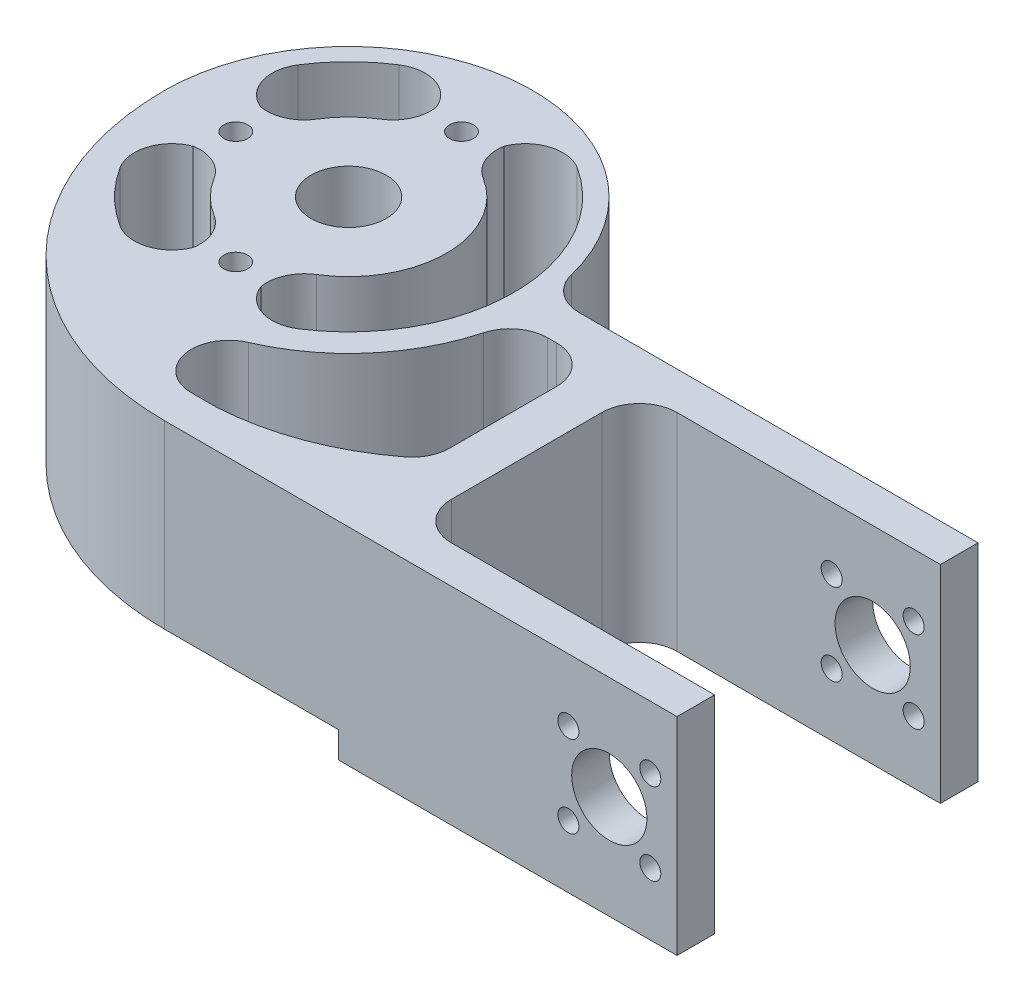
SolidWorks part; units mm, degrees
material "6061-T6 (SS)"
ref_plane "Front Plane" through (0, 0, 0) normal (0, 0, 1) x (1, 0, 0)
ref_plane "Top Plane" through (0, 0, 0) normal (0, 1, 0) x (1, 0, 0)
ref_plane "Right Plane" through (0, 0, 0) normal (1, 0, 0) x (0, 0, -1)
sketch "Sketch1" plane through (0, 0, 0) normal (0, 1, 0) x (1, 0, 0)
  circle A0 centre (0, 0) radius 31.0896
  dimension "D1" = 62.1792
extrude "Boss-Extrude1" add sketch "Sketch1" along normal blind 34.925
sketch "Sketch2" plane through (0, 34.925, 0) normal (0, 1, 0) x (1, 0, 0)
  line L0 (0, 0) -> (-31.0896, 0) construction
  line L1 (0, 0) -> (30.9857, 2.54) construction
  line L2 (46.5427, -48.26) -> (17.1704, -48.26)
  line L4 (46.5427, -48.26) -> (46.5427, 2.54)
  line L7 (30.9857, 2.54) -> (46.5427, 2.54)
  circle A0 centre (0, 0) radius 31.0896 construction
  arc A1 (17.1704, -48.26) -> (-31.0896, 0) centre (17.1704, 0) cw
  circle A2 centre (0, 0) radius 31.0896
  arc A3 (-31.0896, 0) -> (30.9857, 2.54) centre (0, 0) ccw
  dimension "D3" = 2.54
  dimension "D1" = 50.8
  dimension "D2" = 15.557
  dimension "D4" = 0
extrude "Boss-Extrude2" add sketch "Sketch2" against normal blind 30.48
sketch "Sketch3" plane through (0, 34.925, 0) normal (0, 1, 0) x (1, 0, 0)
  line L0 (46.5427, -0.3336) -> (46.5427, -48.26)
  line L1 (17.1704, -48.26) -> (46.5427, -48.26) construction
  line L2 (46.5427, -48.26) -> (103.6927, -48.26)
  line L3 (103.6927, -48.26) -> (103.6927, -41.91)
  line L4 (103.6927, -41.91) -> (52.8927, -41.91)
  line L5 (52.8927, -41.91) -> (52.8927, -3.81)
  line L6 (52.8927, -3.81) -> (103.6927, -3.81)
  line L7 (103.6927, -3.81) -> (103.6927, 2.54)
  line L8 (103.6927, 2.54) -> (46.5427, 2.54)
  line L9 (46.5427, -0.3336) -> (46.5427, 2.54)
  line L10 (46.5427, -48.26) -> (46.5427, 2.54) construction
  dimension "D1" = 57.15
  dimension "D2" = 38.1
  dimension "D3" = 6.35
  dimension "D4" = 6.35
extrude "Boss-Extrude3" add sketch "Sketch3" against normal up to surface (34.925 mm away) up to face at (0, 0, 31.0896)
sketch "Sketch4" plane through (0, 0, -2.54) normal (0, 0, -1) x (-1, 0, 0)
  line L0 (-103.6927, 17.4625) -> (-92.2627, 17.4625) construction
  line L1 (-103.6927, 0) -> (-103.6927, 34.925) construction
  line L2 (-92.2627, 17.4625) -> (-99.1775, 10.5477) construction
  line L3 (-92.2627, 17.4625) -> (-99.1775, 24.3773) construction
  line L4 (-92.2627, 17.4625) -> (-99.1775, 10.5477) construction
  line L5 (-92.2627, 17.4625) -> (-85.3479, 10.5477) construction
  line L6 (-92.2627, 17.4625) -> (-85.3479, 24.3773) construction
  line L8 (-99.1775, 24.3773) -> (-103.6927, 24.3773) construction
  line L9 (-103.6927, 0) -> (-103.6927, 34.925) construction
  line L10 (-99.1775, 10.5477) -> (-103.6927, 10.5477) construction
  circle A0 centre (-92.2627, 17.4625) radius 6.35
  circle A1 centre (-85.3479, 10.5477) radius 1.778
  circle A3 centre (-99.1775, 24.3773) radius 1.778
  circle A4 centre (-99.1775, 10.5477) radius 1.778
  circle A5 centre (-85.3479, 24.3773) radius 1.778
  dimension "D1" = 11.43
  dimension "D2" = 12.7
  dimension "D3" = 3.556
  dimension "D5" = 19.558
  dimension "D4" = 19.558
extrude "Cut-Extrude1" cut sketch "Sketch4" against normal up to surface (50.8 mm away) up to face at (53.3542, 12.7529, 48.26)
fillet "Fillet8" radius 6.35 1 edges at (30.9857, 19.685, -2.54)
fillet "Fillet9" radius 6.35 1 edges at (52.8927, 17.4625, 41.91)
fillet "Fillet10" radius 6.35 1 edges at (52.8927, 17.4625, 3.81)
sketch "Sketch11" plane through (0, 4.445, 0) normal (0, -1, 0) x (-1, 0, 0)
  line L0 (-46.5427, -48.26) -> (-46.5427, 2.54)
  line L1 (-103.6927, -3.81) -> (-32.1601, -3.81)
  line L2 (-103.6927, -41.91) -> (-14.7927, -41.91)
  line L3 (-18.1864, 0) -> (-32.385, 0) construction
  line L4 (-45.2727, -3.81) -> (-45.2727, -31.1827)
  circle A0 centre (0, 0) radius 32.385
  arc A2 (-17.1704, -48.26) -> (31.0896, 0) centre (-17.1704, 0) ccw construction
  circle A3 centre (-17.1704, 0) radius 41.9774
  dimension "D1" = 64.77
  dimension "D3" = 88.9
  dimension "D2" = 14.1986
  dimension "D4" = 1.27
sketch "Sketch12" plane through (0, 0, 0) normal (0, -1, 0) x (1, 0, 0)
  line L0 (0, 0) -> (0, -19.05) construction
  line L1 (0, 0) -> (0, 19.05) construction
  line L2 (0, 0) -> (-19.05, 0) construction
  line L3 (0, 0) -> (19.05, 0) construction
  circle A0 centre (0, 19.05) radius 2.0193
  circle A1 centre (-19.05, 0) radius 2.0193
  circle A2 centre (0, -19.05) radius 2.0193
  dimension "D1" = 4.0386
  dimension "D2" = 19.05
extrude "Cut-Extrude7" cut sketch "Sketch12" against normal up to surface (34.925 mm away) up to face at (56.2464, 34.925, 17.0919)
extrude "Cut-Extrude8" cut sketch "Sketch11" against normal through all contours L0 A3 L2 A0 L1 region at (27.27, 4.445, 26.5567)
fillet "Fillet11" radius 6.35 4 edges at (32.1601, 19.685, 3.81) (-12.1864, 19.685, 30.0047) (45.2727, 19.685, 31.1827) (45.2727, 19.685, 3.81)
sketch "Sketch14" plane through (0, 0, 0) normal (0, -1, 0) x (1, 0, 0)
  line L0 (0, 0) -> (-10.414, -10.414) construction
  line L1 (-10.414, -10.414) -> (10.414, -10.414)
  line L2 (-10.414, -10.414) -> (-10.414, 10.414)
  line L3 (-10.414, 10.414) -> (10.414, 10.414)
  line L4 (10.414, -10.414) -> (10.414, 10.414)
  line L5 (0, 0) -> (10.414, 10.414) construction
  line L6 (-10.414, 10.414) -> (0, 0) construction
  line L7 (0, 0) -> (10.414, -10.414) construction
  arc A0 (10.414, -10.414) -> (10.414, 10.414) centre (10.414, 0) ccw
  circle A1 centre (0, 0) radius 6.35
  dimension "D1" = 12.7
  dimension "D3" = 20.828
sketch "Sketch13" plane through (0, 0, 0) normal (0, -1, 0) x (1, 0, 0)
  line L0 (0, 0) -> (7.4507, 26.9283)
  line L1 (0, 0) -> (7.4507, -26.9283)
  line L2 (0, 0) -> (-7.4507, 26.9283)
  line L3 (0, 0) -> (-26.9283, 7.4507)
  line L4 (0, 0) -> (-26.9283, -7.4507)
  line L5 (0, 0) -> (-7.4507, -26.9283)
  line L6 (0, 0) -> (26.9283, 7.4507)
  line L7 (0, 0) -> (27.166, -6.531)
  circle A0 centre (0, 0) radius 27.94
  circle A1 centre (0, 0) radius 16.51
  circle A2 centre (0, 19.05) radius 2.0193 construction
  circle A3 centre (0, -19.05) radius 2.0193 construction
  circle A4 centre (-19.05, 0) radius 2.0193 construction
  circle A5 centre (-19.05, 0) radius 2.0193 construction
  dimension "D1" = 55.88
  dimension "D2" = 33.02
  dimension "D3" = 5.08
  dimension "D4" = 5.08
  dimension "D5" = 5.08
  dimension "D6" = 5.08
  dimension "D7" = 5.08
  dimension "D8" = 5.08
  dimension "D9" = 13.9817
extrude "Cut-Extrude9" cut sketch "Sketch13" against normal through all contours A1 L2 A0 L3 | A1 L4 A0 L5 | A1 L1 A0 L7 | A1 L6 A0 L0 | L7 A0 L6 region at (15.3599, 0, 15.3599) region at (15.5716, 0, -15.051) region at (-15.3599, 0, 15.3599) region at (-15.3599, 0, -15.3599) region at (22.4702, 0, 0.382)
fillet "Fillet14" radius 6.35 12 edges at (4.4027, 17.4625, 15.9122) (7.4507, 17.4625, 26.9283) (-26.9283, 17.4625, 7.4507) (-4.4027, 17.4625, 15.9122) (-15.9122, 17.4625, 4.4027) (-7.4507, 17.4625, 26.9283) (-7.4507, 17.4625, -26.9283) (-26.9283, 17.4625, -7.4507) (-4.4027, 17.4625, -15.9122) (-15.9122, 17.4625, -4.4027) (7.4507, 17.4625, -26.9283) (4.4027, 17.4625, -15.9122)
extrude "Cut-Extrude10" cut sketch "Sketch14" against normal blind 12.7 contours L1 L4 L3 L2 | L4 A0 region at (-10.1194, 0, 0) region at (14.8338, 0, 0)
fillet "Fillet17" radius 2.54 2 edges at (13.0872, 6.35, -10.0651) (13.0872, 6.35, 10.0651)
extrude "Cut-Extrude11" cut sketch "Sketch14<3>" against normal through all contours A1 region at (0, 0, 0)
sketch "Sketch14<3>" plane through (0, 0, 0) normal (0, -1, 0) x (1, 0, 0) same geometry as "Sketch14"
